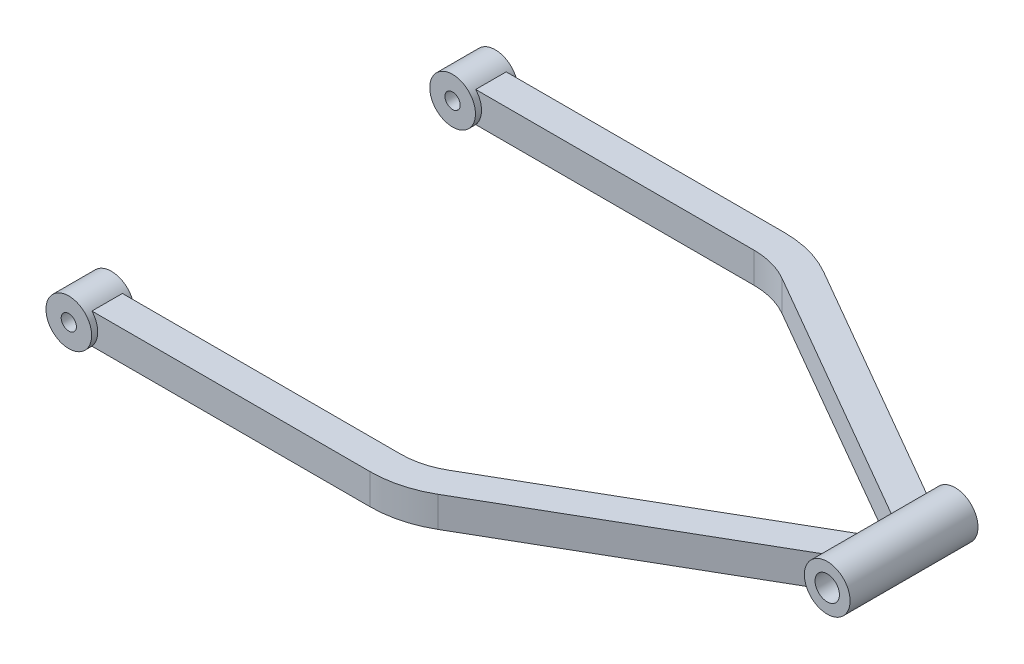
SolidWorks part; units mm, degrees
material "1060 Alloy"
ref_plane "Front Plane" through (0, 0, 0) normal (0, 0, 1) x (1, 0, 0)
ref_plane "Top Plane" through (0, 0, 0) normal (0, 1, 0) x (1, 0, 0)
ref_plane "Right Plane" through (0, 0, 0) normal (1, 0, 0) x (0, 0, -1)
sketch "Sketch1" plane through (0, 0, 0) normal (0, 1, 0) x (1, 0, 0)
  line L0 (0, 0) -> (200, 0) construction
  line L1 (0, 63) -> (96.9615, 63)
  line L2 (111.9615, 58.9808) -> (200, 8.1517)
  arc A0 (96.9615, 63) -> (111.9615, 58.9808) centre (96.9615, 33) cw
  point P8 (105, 63)
  dimension "D5" = 30
  dimension "D1" = 200
  dimension "D2" = 105
  dimension "D3" = 63
  dimension "D4" = 150
ref_plane "Plane1" through (0, 0, -63) normal (0, 0, 1) x (1, 0, 0)
sketch "Sketch2" plane through (0, 0, -63) normal (0, 0, 1) x (1, 0, 0)
  circle A0 centre (0, 0) radius 7.5
  circle A1 centre (0, 0) radius 2.5
  dimension "D1" = 15
  dimension "D2" = 5
extrude "Boss-Extrude1" add sketch "Sketch2" along normal mid plane 14
ref_plane "Plane2" through (0, 0, -63) normal (1, 0, 0) x (0, 0, -1)
sketch "Sketch3" plane through (0, 0, -63) normal (1, 0, 0) x (0, 0, -1)
  line L1 (-5, -5) -> (5, -5)
  line L2 (-5, -5) -> (-5, 5)
  line L3 (-5, 5) -> (5, 5)
  line L4 (5, -5) -> (5, 5)
  line L5 (-5, -5) -> (5, 5) construction
  line L6 (-5, 5) -> (5, -5) construction
  point P0 (0, 0)
  dimension "D1" = 10
sketch "Sketch4" plane through (0, 0, 0) normal (0, 0, 1) x (1, 0, 0)
  line L0 (111.9615, 0) -> (200, 0) construction
  circle A0 centre (200, 0) radius 7.5
  circle A1 centre (200, 0) radius 4
  dimension "D1" = 8
  dimension "D2" = 15
extrude "Boss-Extrude2" add sketch "Sketch4" along normal mid plane 42 separate body
sweep "Sweep1" add profiles "Sketch3" path "Sketch1"
mirror "Mirror1" about plane through (0, 0, 0) normal (0, 0, 1) of "Sweep1", "Boss-Extrude1"
extrude "Cut-Extrude1" cut sketch "Sketch2<2>" along normal blind 137 and the other way blind 20 contours A1 region at (0, 0, -63)
sketch "Sketch2<2>" plane through (0, 0, -63) normal (0, 0, 1) x (1, 0, 0) same geometry as "Sketch2"
extrude "Cut-Extrude2" cut sketch "Sketch4<2>" against normal mid plane 60 contours A1 region at (200, 0, 0)
sketch "Sketch4<2>" plane through (0, 0, 0) normal (0, 0, 1) x (1, 0, 0) same geometry as "Sketch4"
equation "\"D3@Sketch1\"=126/2"
